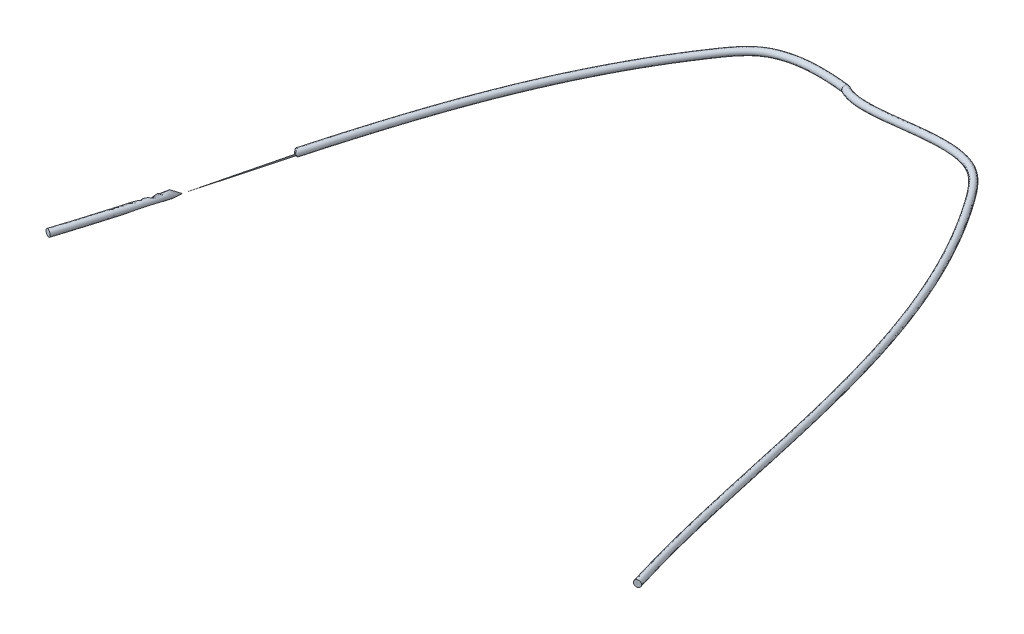
SolidWorks part; units mm, degrees
ref_plane "Front Plane" through (0, 0, 0) normal (0, 0, 1) x (1, 0, 0)
ref_plane "Top Plane" through (0, 0, 0) normal (0, 1, 0) x (1, 0, 0)
ref_plane "Right Plane" through (0, 0, 0) normal (1, 0, 0) x (0, 0, -1)
ref_plane "Plane1" through (0, 20.5189, 0) normal (0, 1, 0) x (1, 0, 0)
sketch "Sketch56" plane through (0, 20.5189, 0) normal (0, 1, 0) x (1, 0, 0)
  arc A2 (-15.6293, 16.1485) -> (-16.2695, 13.0158) centre (-6.278, 12.6057) ccw construction
  arc A3 (8.1975, 54.6974) -> (-0.6338, 48.7338) centre (8.5177, 44.7026) ccw construction
  spline S0 degree 3 poles (14.3142, 54.5694) (10.969, 54.9401) (3.9561, 55.3371) (-15.359, 28.4652) (-19.2661, 0.1042) (-27.3147, -24.9182) knots 0 0 0 0 0.119969 0.175941 1 1 1 1
sketch "Sketch19" plane through (0, 20.5189, 0) normal (0, 1, 0) x (1, 0, 0)
  arc A2 (53.7305, 13.0158) -> (53.1636, 15.9824) centre (43.7374, 12.6437) ccw construction
  arc A3 (28.8375, 54.6974) -> (26.0834, 51.7075) centre (29.0834, 51.7075) ccw construction
  arc A4 (38.6757, 48.8215) -> (30.4819, 54.6974) centre (29.546, 44.7413) ccw construction
  spline S0 degree 3 poles (14.3142, 54.5694) (18.7956, 51.9708) (31.6749, 58.1666) (54.4253, 28.7017) (55.7076, -0.9697) (63.5425, -26.2905) knots 0 0 0 0 0.189709 0.246928 1 1 1 1
sweep "Sweep2" add path "Sketch19" circular profile diameter 1 parameters "D3"=1
sweep "Sweep3" add path "Sketch56" circular profile diameter 1 parameters "D3"=1
